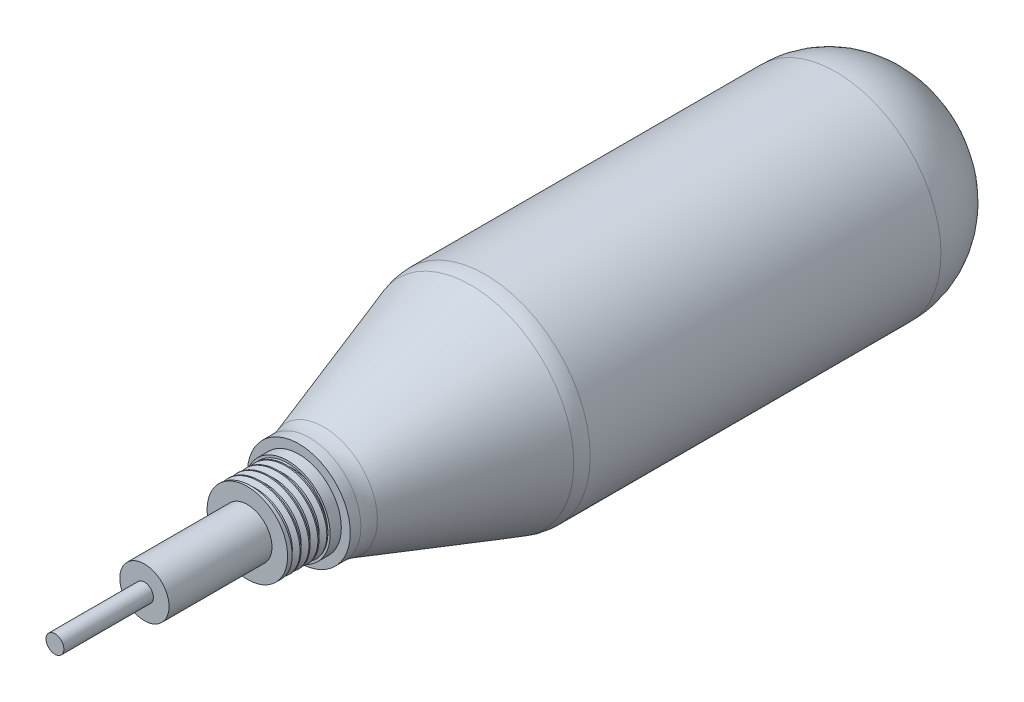
SolidWorks part; units mm, degrees
ref_plane "Plan de face" through (0, 0, 0) normal (0, 0, 1) x (1, 0, 0)
ref_plane "Plan de dessus" through (0, 0, 0) normal (0, 1, 0) x (1, 0, 0)
ref_plane "Plan de droite" through (0, 0, 0) normal (1, 0, 0) x (0, 0, -1)
sketch "Esquisse2" plane through (0, 0, 0) normal (1, 0, 0) x (0, 0, -1)
  line L0 (0, 0) -> (151.5, 0)
  line L1 (151.5, 0) -> (151.5, 3.5)
  line L2 (131.5, 23.5) -> (53.1228, 23.5)
  line L3 (49.9605, 22.9868) -> (17.0395, 12.0132)
  line L4 (13.8772, 11.5) -> (11.5, 11.5)
  line L5 (11.5, 11.5) -> (11.5, 9.5)
  line L6 (11.5, 9.5) -> (9, 9.5)
  line L7 (9, 9.5) -> (9, 9)
  line L8 (9, 9) -> (0, 9)
  line L9 (0, 9) -> (0, 5.5)
  line L10 (0, 0) -> (178.5381, 0) construction
  line L11 (0, 5.5) -> (-23, 5.5)
  line L12 (-23, 5.5) -> (-23, 2)
  line L13 (-23, 0) -> (0, 0)
  line L14 (-23, 0) -> (-43, 0)
  line L15 (-43, 0) -> (-43, 2)
  line L16 (-43, 2) -> (-23, 2)
  arc A0 (17.0395, 12.0132) -> (13.8772, 11.5) centre (13.8772, 21.5) cw
  arc A1 (53.1228, 23.5) -> (49.9605, 22.9868) centre (53.1228, 13.5) ccw
  arc A2 (151.5, 3.5) -> (131.5, 23.5) centre (131.5, 3.5) ccw
  point P14 (15.5, 11.5)
  point P17 (51.5, 23.5)
  point P21 (151.5, 23.5)
  dimension "D10" = 10
  dimension "D11" = 10
  dimension "D12" = 20
  dimension "D2" = 40
  dimension "D3" = 23.5
  dimension "D4" = 11.5
  dimension "D5" = 9.5
  dimension "D6" = 9
  dimension "D7" = 2.5
  dimension "D8" = 4
  dimension "D9" = 100
  dimension "D13" = 9
  dimension "D14" = 23
  dimension "D15" = 5.5
  dimension "D16" = 20
  dimension "D17" = 2
revolve "Révolution1" add sketch "Esquisse2" angle 360 about L10
thread "Filetage1" pitch 2 method cut profile "Profil de filetage1" start angle 0, offset 0, length 0, pitch 2, diameter 18
ref_plane "Plan1" through (-9, 0, 0) normal (0, -1, 0) x (-1, 0, 0)
sketch "Profil de filetage1" plane through (-9, 0, 0) normal (0, -1, 0) x (-1, 0, 0)
  line L0 (0, 0) -> (0, 2) construction
  line L11 (0, 0) -> (0, 1.75)
  line L12 (0, 1.75) -> (-1.0825, 1.125)
  line L13 (-1.0825, 1.125) -> (-1.0825, 0.625)
  line L15 (-1.0825, 0.625) -> (0, 0)
  line L17 (-1.0825, 0.875) -> (0, 0.875) construction
  point P2 (0, 0)
  dimension "Pitch" = 2
  dimension "Profile_Angle" = 60
  dimension "Profile_Land" = 0.5
  dimension "Profile_Height" = 1.0825
